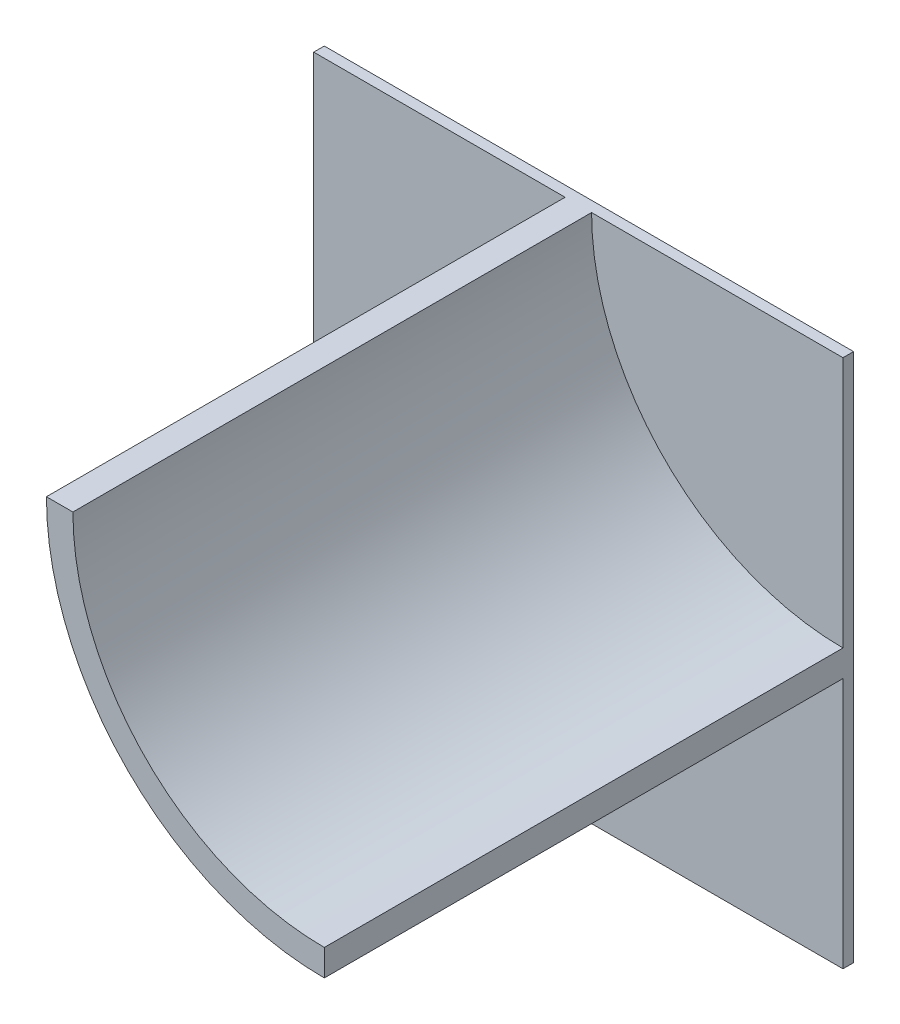
SolidWorks part; units mm, degrees
ref_plane "Płaszczyzna przednia" through (0, 0, 0) normal (0, 0, 1) x (1, 0, 0)
ref_plane "Płaszczyzna górna" through (0, 0, 0) normal (0, 1, 0) x (1, 0, 0)
ref_plane "Płaszczyzna prawa" through (0, 0, 0) normal (1, 0, 0) x (0, 0, -1)
sketch "Szkic1" plane through (0, 0, 0) normal (0, 0, 1) x (1, 0, 0)
  line L0 (0, 0) -> (100, 0)
  line L1 (0, 0) -> (-100, 0)
  line L2 (0, 0) -> (0, 100)
  line L3 (0, 0) -> (0, -100)
  line L4 (0, 100) -> (100, 100)
  line L5 (100, 100) -> (100, 0)
  line L6 (100, -100) -> (0, -100)
  line L7 (100, 0) -> (100, -100)
  line L8 (0, 100) -> (-100, 100)
  line L9 (-100, 100) -> (-100, 0)
  line L10 (-100, -100) -> (-100, 0)
  line L11 (0, -100) -> (-100, -100)
  dimension "D1" = 100
  dimension "D2" = 100
  dimension "D3" = 100
  dimension "D4" = 100
  dimension "D5" = 100
  dimension "D6" = 100
  dimension "D7" = 100
  dimension "D8" = 100
  dimension "D9" = 100
  dimension "D10" = 100
  dimension "D11" = 100
extrude "Dodanie-wyciągnięcie1" add sketch "Szkic1" along normal blind 4 contours L8 L9 L1 L2 | L5 L4 L2 L0 | L7 L0 L3 L6 | L11 L3 L1 L10 region at (50, 50, 0) region at (-50, -50, 0) region at (-50, 50, 0) region at (50, -50, 0)
sketch "Szkic2" plane through (0, 0, 4) normal (0, 0, 1) x (1, 0, 0)
  line L2 (100, -100) -> (-100, -100) construction
  line L9 (-2, -100) -> (2, -100)
  line L20 (0, 0) -> (0, 100)
  line L23 (100, 100) -> (-100, 100) construction
  line L24 (0, 0) -> (100, 0)
  line L25 (100, 100) -> (100, -100) construction
  line L26 (100, 0) -> (100, 5)
  line L27 (100, 0) -> (100, -5)
  line L28 (0, 100) -> (5, 100)
  line L29 (0, 100) -> (-5, 100)
  circle A0 centre (100, 100) radius 95
  circle A1 centre (100, 100) radius 105
  line M10 (100, -100) -> (100, 100)
  line M11 (100, 100) -> (-100, 100)
  dimension "D1" = 5
  dimension "D2" = 5
  dimension "D3" = 5
  dimension "D4" = 5
  dimension "D8" = 4
extrude "Dodanie-wyciągnięcie5" add sketch "Szkic2" along normal blind 196 contours L20 A1 L24 A0 M10 M11 | L24 A1 M10 | A1 L20 M11 region at (-2.0041, 87.9551, 4) region at (1.4142, 83.9922, 4) region at (87.9551, -2.0041, 4)
